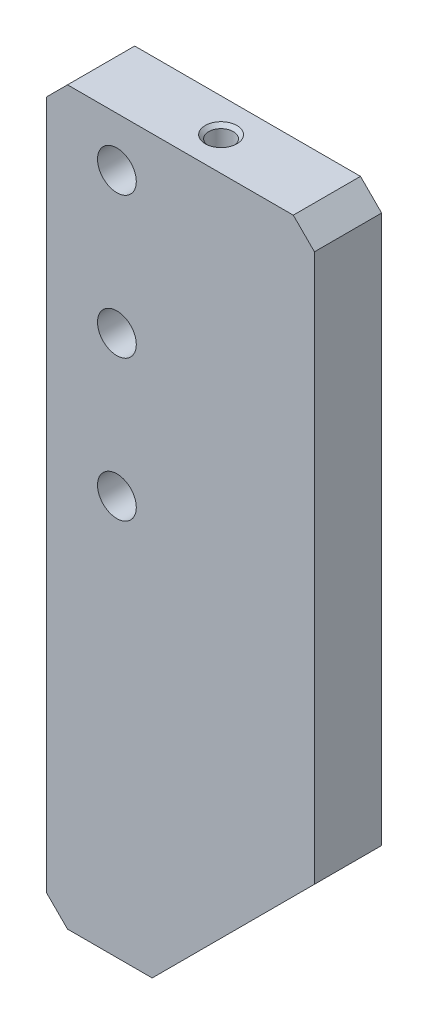
SolidWorks part; units mm, degrees
material "Plain Carbon Steel"
ref_plane "Front Plane" through (0, 0, 0) normal (0, 0, 1) x (1, 0, 0)
ref_plane "Top Plane" through (0, 0, 0) normal (0, 1, 0) x (1, 0, 0)
ref_plane "Right Plane" through (0, 0, 0) normal (1, 0, 0) x (0, 0, -1)
sketch "Sketch1" plane through (0, 0, 0) normal (0, 0, 1) x (1, 0, 0)
  line L1 (-185.2477, 113.1924) -> (-185.2477, 9.5523) construction
  line L2 (-185.2477, 113.1924) -> (-147.2477, 113.1924) construction
  line L5 (-147.2477, 113.1924) -> (-147.2477, 32.5523) construction
  line L7 (-163.7477, 125.1924) -> (-163.7477, 113.1924) construction
  line L8 (-165.2477, 125.1924) -> (-165.2477, 113.1924) construction
  line L9 (-166.7477, 125.1924) -> (-166.7477, 113.1924) construction
  line L10 (-170.2477, 9.5523) -> (-185.2477, 9.5523)
  line L11 (-185.2477, 113.1924) -> (-185.2477, 9.5523)
  line L12 (-185.2477, 113.1924) -> (-147.2477, 113.1924)
  line L15 (-147.2477, 113.1924) -> (-147.2477, 32.5523)
  line L16 (-147.2477, 32.5523) -> (-170.2477, 9.5523)
  line L17 (-163.7477, 125.1924) -> (-163.7477, 113.1924) construction
  line L18 (-165.2477, 125.1924) -> (-165.2477, 113.1924) construction
  line L19 (-166.7477, 125.1924) -> (-166.7477, 113.1924) construction
  line L20 (-163.7477, 113.1924) -> (-163.7477, 93.1924) construction
  line L21 (-163.7477, 93.1924) -> (-165.2477, 92.3264) construction
  line L22 (-165.2477, 92.3264) -> (-166.7477, 93.1924) construction
  line L23 (-166.7477, 93.1924) -> (-166.7477, 113.1924) construction
  line L24 (-163.7477, 93.1924) -> (-166.7477, 93.1924) construction
  circle A0 centre (-175.2477, 66.1924) radius 2.75 construction
  circle A1 centre (-175.2477, 86.1924) radius 2.75 construction
  circle A2 centre (-175.2477, 106.1924) radius 2.75 construction
  circle A3 centre (-169.2477, 106.1924) radius 2.75 construction
  circle A4 centre (-175.2477, 66.1924) radius 2.75
  circle A5 centre (-175.2477, 86.1924) radius 2.75
  circle A6 centre (-175.2477, 106.1924) radius 2.75
  circle A7 centre (-169.2477, 106.1924) radius 2.75 construction
  dimension "D1" = 120
  dimension "D2" = 20
extrude "Boss-Extrude1" add sketch "Sketch1" along normal blind 4.7625 and the other way blind 4.7625
sketch "Sketch2" plane through (0, 0, 0) normal (0, 0, 1) x (1, 0, 0)
  line L0 (-165.2477, 113.1924) -> (-166.9977, 113.1924)
  line L1 (-166.9977, 113.1924) -> (-166.9977, 108.1924)
  line L2 (-166.9977, 108.1924) -> (-166.4477, 107.8748)
  line L3 (-166.4477, 107.8748) -> (-166.4477, 93.0192)
  line L4 (-166.4477, 93.0192) -> (-165.2477, 92.3264)
  line L5 (-165.2477, 113.1924) -> (-165.2477, 92.3264)
  line L6 (-147.2477, 113.1924) -> (-185.2477, 113.1924) construction
  line L7 (-165.2477, 113.1924) -> (-165.2477, 95.5113) construction
  line L8 (-185.2477, 113.1924) -> (-147.2477, 113.1924) construction
  line L9 (-165.2477, 125.1924) -> (-165.2477, 113.1924) construction
  line L10 (-165.2477, 92.3264) -> (-166.7477, 93.1924) construction
  dimension "D1" = 3.5
  dimension "D2" = 5
  dimension "D3" = 2.4
revolve "Cut-Revolve1" cut sketch "Sketch2" angle 360 about L7
chamfer "Chamfer1" distance 3 angle 45 3 edges at (-185.2477, 9.5523, 0) (-185.2477, 113.1924, 0) (-147.2477, 113.1924, 0)
chamfer "Chamfer2" distance 0.5 angle 45 1 edges at (-166.9977, 113.1924, 0)
